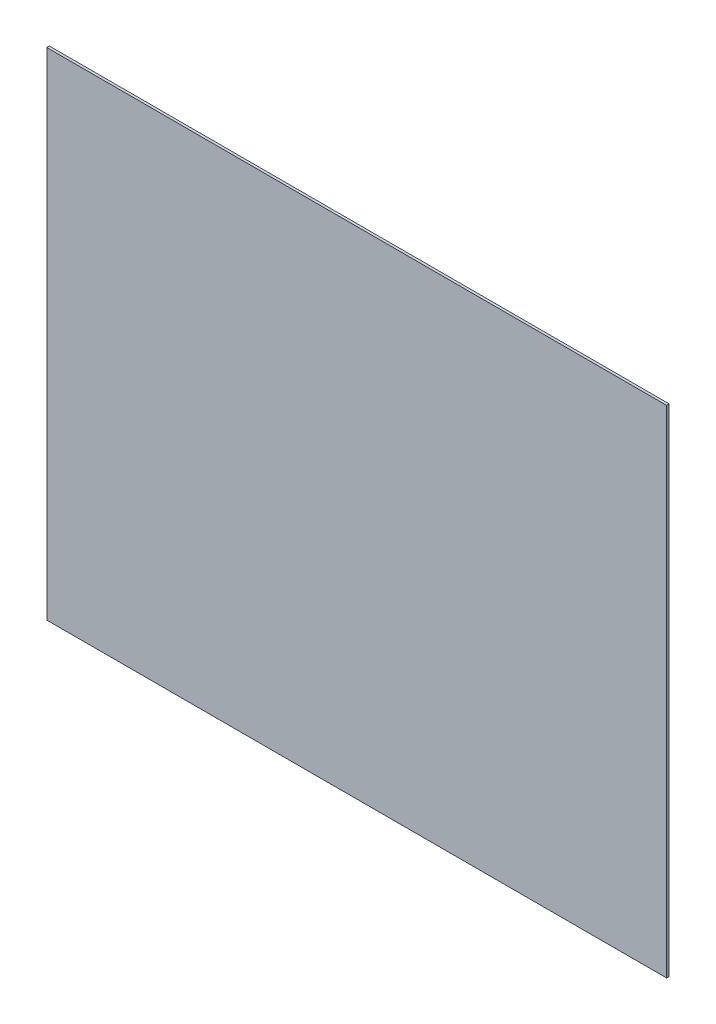
SolidWorks part; units mm, degrees
ref_plane "Front Plane" through (0, 0, 0) normal (0, 0, 1) x (1, 0, 0)
ref_plane "Top Plane" through (0, 0, 0) normal (0, 1, 0) x (1, 0, 0)
ref_plane "Right Plane" through (0, 0, 0) normal (1, 0, 0) x (0, 0, -1)
sketch "Sketch1" plane through (0, 0, 0) normal (0, 0, 1) x (1, 0, 0)
  line L1 (-238.8538, 271.0227) -> (523.1462, 271.0227)
  line L2 (-238.8538, 271.0227) -> (-238.8538, -338.5773)
  line L3 (-238.8538, -338.5773) -> (523.1462, -338.5773)
  line L4 (523.1462, 271.0227) -> (523.1462, -338.5773)
  dimension "D1" = 762
  dimension "D2" = 609.6
extrude "Boss-Extrude1" add sketch "Sketch1" along normal blind 3.175
